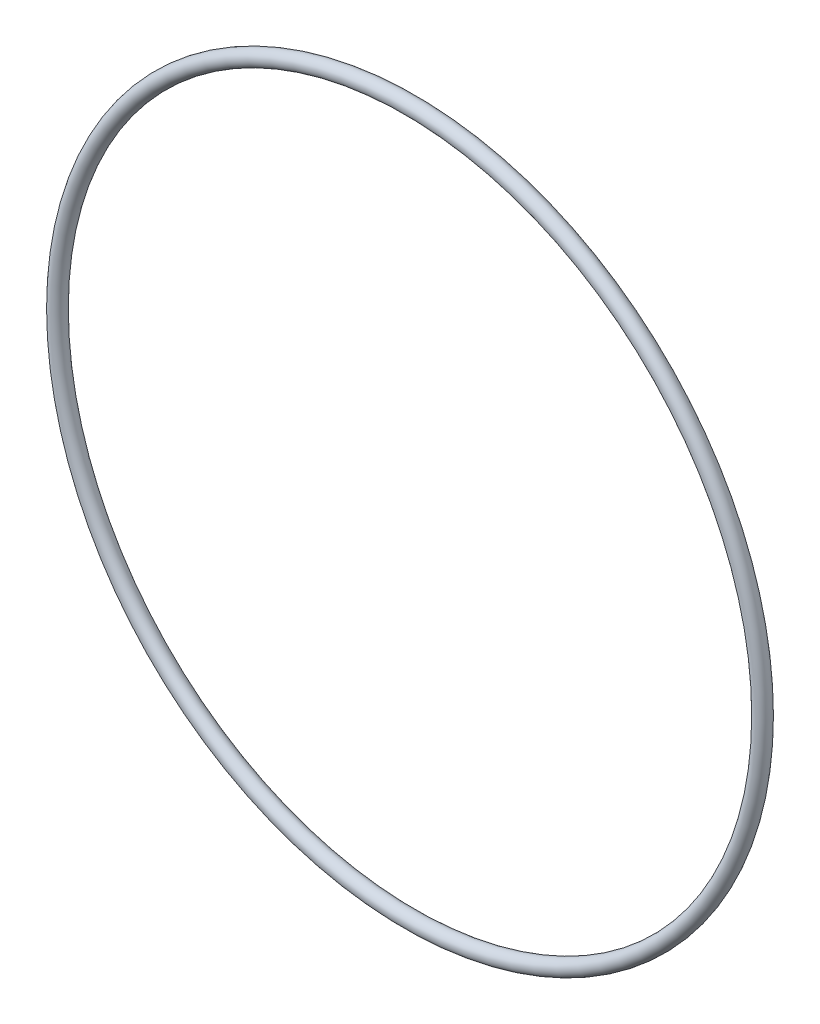
SolidWorks part; units mm, degrees
material "O-Ring (NBR)"
ref_plane "Front Plane" through (0, 0, 0) normal (0, 0, 1) x (1, 0, 0)
ref_plane "Top Plane" through (0, 0, 0) normal (0, 1, 0) x (1, 0, 0)
ref_plane "Right Plane" through (0, 0, 0) normal (1, 0, 0) x (0, 0, -1)
sketch "Sketch1" plane through (0, 0, 0) normal (1, 0, 0) x (0, 0, -1)
  line L0 (0, 0) -> (-13.4105, 0) construction
  circle A0 centre (0, 68.75) radius 1.5
  dimension "DIA" = 3
  dimension "ID" = 134.5
revolve "Revolve1" add sketch "Sketch1" angle 360 about L0
ref_axis "Axis1" through (0, 0, -1.65) along (0, 0, 1)
